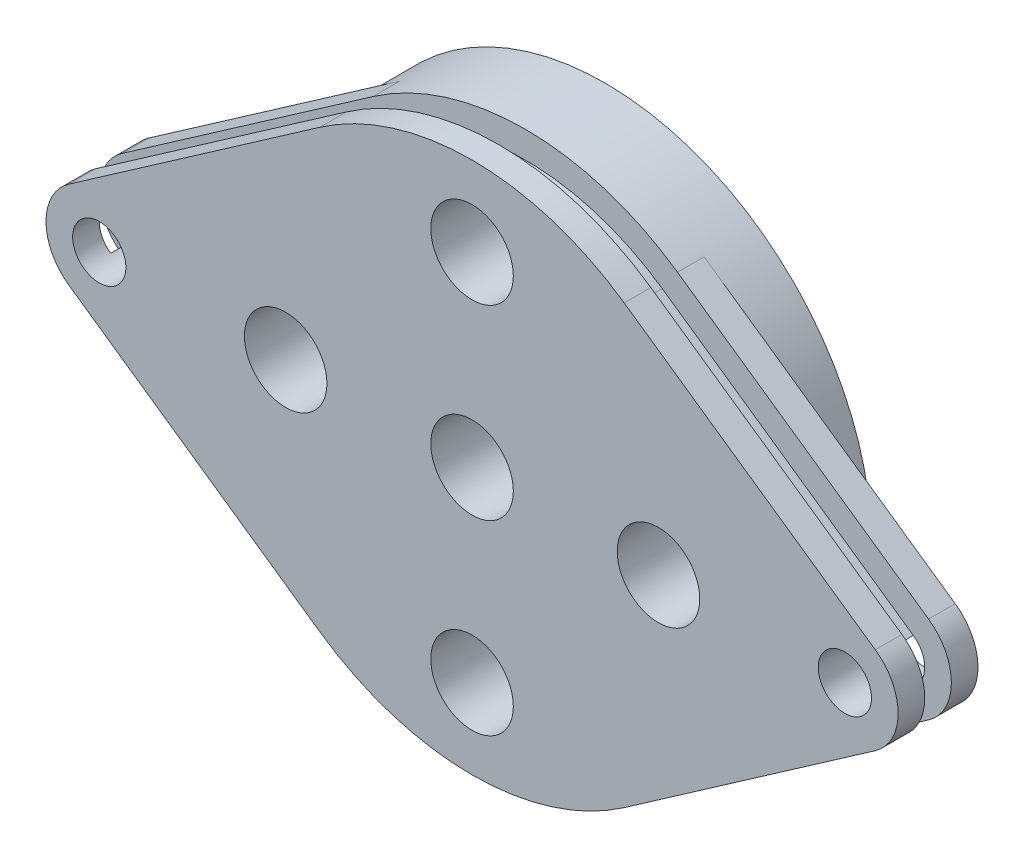
SolidWorks part; units mm, degrees
ref_plane "前视基准面" through (0, 0, 0) normal (0, 0, 1) x (1, 0, 0)
ref_plane "上视基准面" through (0, 0, 0) normal (0, 1, 0) x (1, 0, 0)
ref_plane "右视基准面" through (0, 0, 0) normal (1, 0, 0) x (0, 0, -1)
other "Configuration Table"
sketch "草图1" plane through (0, 0, 0) normal (0, 0, 1) x (1, 0, 0)
  circle A0 centre (0, 0) radius 10
  circle A1 centre (0, 0) radius 1.55
  circle A2 centre (0, 0) radius 7 construction
  circle A3 centre (-7, 0) radius 1.55
  circle A4 centre (0, 7) radius 1.55
  circle A5 centre (7, 0) radius 1.55
  circle A6 centre (0, -7) radius 1.55
  point P16 (0, 0)
  dimension "D1" = 20
  dimension "D2" = 3.1
  dimension "D3" = 14
  dimension "D4" = 4
extrude "凸台-拉伸1" add sketch "草图1" along normal blind 2
sketch "草图2" plane through (0, 0, 2) normal (0, 0, 1) x (1, 0, 0)
  line L0 (0, 0) -> (0, -50000) construction
  line L1 (-5.7143, 8.2065) -> (-15.1429, 1.6413)
  line L2 (0, 0) -> (50000, 0) construction
  line L3 (-5.7143, -8.2065) -> (-15.1429, -1.6413)
  line L4 (5.7143, -8.2065) -> (15.1429, -1.6413)
  line L5 (5.7143, 8.2065) -> (15.1429, 1.6413)
  line L6 (5.1429, -7.3859) -> (14.5714, -0.8207)
  line L7 (5.1429, 7.3859) -> (14.5714, 0.8207)
  line L8 (-5.1429, 7.3859) -> (-14.5714, 0.8207)
  line L9 (-5.1429, -7.3859) -> (-14.5714, -0.8207)
  circle A0 centre (0, 0) radius 10 construction
  arc A1 (-15.1429, 1.6413) -> (-15.1429, -1.6413) centre (-14, 0) ccw
  circle A2 centre (-14, 0) radius 1
  circle A3 centre (14, 0) radius 1
  arc A4 (15.1429, 1.6413) -> (15.1429, -1.6413) centre (14, 0) cw
  arc A5 (-5.7143, 8.2065) -> (5.7143, 8.2065) centre (0, 0) cw
  arc A6 (-5.7143, -8.2065) -> (5.7143, -8.2065) centre (0, 0) ccw
  arc A7 (-5.1429, -7.3859) -> (5.1429, -7.3859) centre (0, 0) ccw
  arc A8 (14.5714, 0.8207) -> (14.5714, -0.8207) centre (14, 0) cw
  arc A9 (-5.1429, 7.3859) -> (5.1429, 7.3859) centre (0, 0) cw
  arc A10 (-14.5714, 0.8207) -> (-14.5714, -0.8207) centre (-14, 0) ccw
  circle M4 centre (7, 0) radius 1.55
  circle M5 centre (-7, 0) radius 1.55
  circle M6 centre (0, 0) radius 10
  circle M7 centre (0, 0) radius 1.55
  circle M8 centre (0, 7) radius 1.55
  circle M9 centre (0, -7) radius 1.55
  dimension "D1" = 14
  dimension "D2" = 2
  dimension "D3" = 2
  dimension "D4" = 1
extrude "凸台-拉伸2" add sketch "草图2" along normal blind 1 contours A2 L8 L1 A1 L3 L9 M6 | A2 L9 L8 M6 | L8 A9 L7 M6 | A9 L8 L9 A7 L6 L7 M6 M5 M7 M9 M8 M4 | A7 L9 L6 M6 | A4 L5 L7 A3 L6 L4 M6 | L6 A3 L7 M6 region at (-7.5481, 6.8512, 2) region at (0, 9.8183, 2) region at (10.3179, 4.765, 2) region at (-11.256, 0, 2) region at (-6.7777, 5.9197, 2) region at (11.256, 0, 2) region at (-7.0353, -6.2896, 2)
extrude "凸台-拉伸3" add sketch "草图2<3>" along normal blind 2 contours A9 L8 L9 A7 L6 L7 M6 M5 M7 M9 M8 M4 | A2 L9 L8 M6 | L6 A3 L7 M6 region at (-11.256, 0, 2) region at (-6.7777, 5.9197, 2) region at (11.256, 0, 2)
sketch "草图2<3>" plane through (0, 0, 2) normal (0, 0, 1) x (1, 0, 0) same geometry as "草图2"
sketch "草图3" plane through (0, 0, 4) normal (0, 0, 1) x (1, 0, 0)
  line L4 (15.1429, 1.6413) -> (5.7143, 8.2065)
  line L5 (-5.7143, 8.2065) -> (-15.1429, 1.6413)
  line L6 (-15.1429, -1.6413) -> (-5.7143, -8.2065)
  line L7 (5.7143, -8.2065) -> (15.1429, -1.6413)
  line L8 (15.1429, 1.6413) -> (5.7143, 8.2065)
  line L9 (-5.7143, 8.2065) -> (-15.1429, 1.6413)
  line L10 (-15.1429, -1.6413) -> (-5.7143, -8.2065)
  line L11 (5.7143, -8.2065) -> (15.1429, -1.6413)
  circle A0 centre (0, 7) radius 1.55 construction
  circle A1 centre (7, 0) radius 1.55 construction
  circle A2 centre (0, -7) radius 1.55 construction
  circle A3 centre (0, 0) radius 1.55 construction
  arc A4 (5.7143, 8.2065) -> (-5.7143, 8.2065) centre (0, 0) ccw
  arc A5 (-15.1429, 1.6413) -> (-15.1429, -1.6413) centre (-14, 0) ccw
  arc A6 (-5.7143, -8.2065) -> (5.7143, -8.2065) centre (0, 0) ccw
  arc A7 (15.1429, -1.6413) -> (15.1429, 1.6413) centre (14, 0) ccw
  arc A8 (5.7143, 8.2065) -> (-5.7143, 8.2065) centre (0, 0) ccw
  arc A9 (-15.1429, 1.6413) -> (-15.1429, -1.6413) centre (-14, 0) ccw
  arc A10 (-5.7143, -8.2065) -> (5.7143, -8.2065) centre (0, 0) ccw
  arc A11 (15.1429, -1.6413) -> (15.1429, 1.6413) centre (14, 0) ccw
  circle A12 centre (-7, 0) radius 1.55 construction
  circle A14 centre (0, 7) radius 1.55
  circle A15 centre (7, 0) radius 1.55
  circle A16 centre (0, -7) radius 1.55
  circle A17 centre (0, 0) radius 1.55
  circle A18 centre (-7, 0) radius 1.55
  circle A19 centre (-14, 0) radius 1
  circle A20 centre (14, 0) radius 1
  dimension "D2" = 2
  dimension "D1" = 0
extrude "凸台-拉伸5" add sketch "草图3" along normal blind 1
